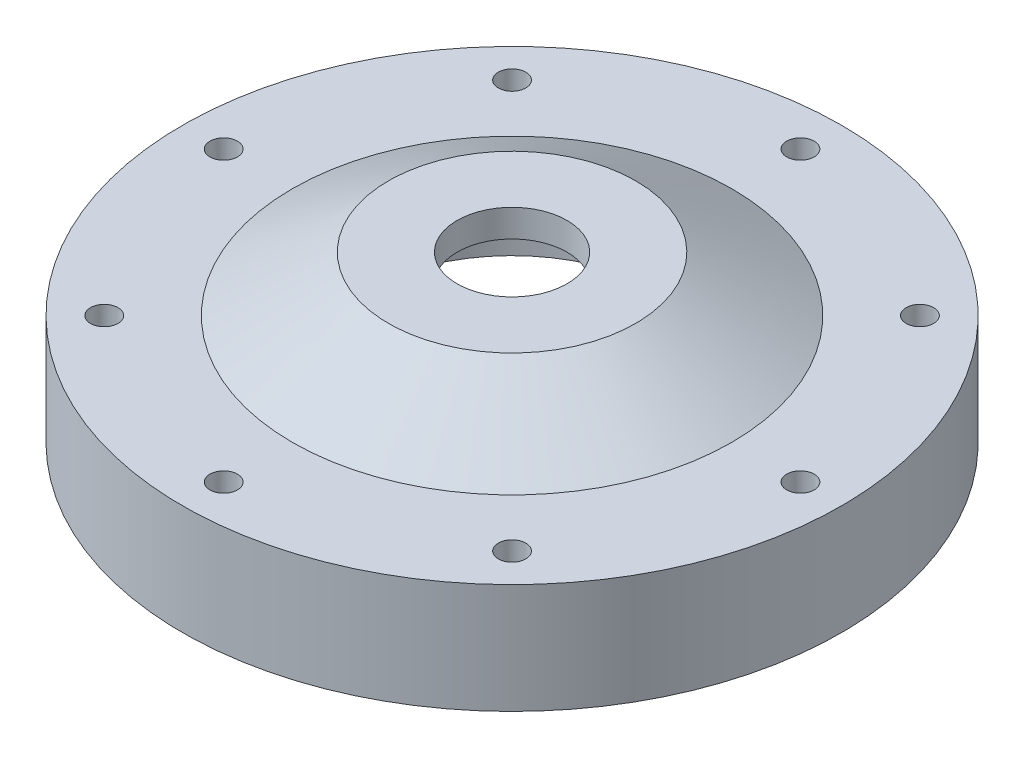
SolidWorks part; units mm, degrees
ref_plane "Front Plane" through (0, 0, 0) normal (0, 0, 1) x (1, 0, 0)
ref_plane "Top Plane" through (0, 0, 0) normal (0, 1, 0) x (1, 0, 0)
ref_plane "Right Plane" through (0, 0, 0) normal (1, 0, 0) x (0, 0, -1)
ref_axis "Axis1" through (0, 35.95, 0) along (0, -1, 0)
sketch "Sketch1" plane through (0, 0, 0) normal (0, 0, 1) x (1, 0, 0)
  line L0 (-12.7, 0) -> (-28.575, 0)
  line L1 (-76.2, -12.7) -> (-76.2, -38.1)
  line L4 (-76.2, -38.1) -> (-58.3057, -38.1)
  line L5 (-53.975, -38.1) -> (-53.975, -25.4)
  line L6 (-34.925, -19.05) -> (-12.7, -6.35)
  line L7 (-12.7, -6.35) -> (-12.7, 0)
  line L9 (0, 0) -> (0, 7.6805) construction
  line L10 (-36.5125, -25.4) -> (-34.925, -25.4)
  line L11 (-34.925, -25.4) -> (-34.925, -19.05)
  line L12 (-55.5625, -38.1) -> (-55.5625, -36.068)
  line L13 (-55.5625, -36.068) -> (-58.3057, -36.068)
  line L14 (-58.3057, -36.068) -> (-58.3057, -38.1)
  line L15 (-53.975, -38.1) -> (-55.5625, -38.1)
  line L16 (-36.5125, -25.4) -> (-36.5125, -23.368)
  line L17 (-36.5125, -23.368) -> (-39.2557, -23.368)
  line L18 (-39.2557, -23.368) -> (-39.2557, -25.4)
  line L19 (-39.2557, -25.4) -> (-53.975, -25.4)
  line L20 (-76.2, -12.7) -> (-50.8, -12.7)
  line L21 (-50.8, -12.7) -> (-28.575, 0)
  dimension "D1" = 34.925
  dimension "D2" = 22.225
  dimension "D3" = 76.2
  dimension "D4" = 2.7432
  dimension "D5" = 38.1
  dimension "D6" = 12.7
  dimension "D7" = 6.35
  dimension "D8" = 12.7
  dimension "D9" = 6.35
  dimension "D10" = 2.7432
  dimension "D11" = 2.032
  dimension "D12" = 1.5875
  dimension "D13" = 2.032
  dimension "D14" = 1.5875
  dimension "D15" = 12.7
  dimension "D16" = 25.4
  dimension "D17" = 15.875
revolve "Revolve1" add sketch "Sketch1" angle 360 about L9
sketch "Sketch2" plane through (0, 0, 0) normal (0, 1, 0) x (1, 0, 0)
  line L0 (0, 0) -> (-66.675, 0) construction
  point P4 (-66.675, 0)
  dimension "D1" = 66.675
hole_wizard "1/4 (0.25) Diameter Hole1" positions "3DSketch1" profile "Sketch3" hole size "1/4" standard "ANSI Inch" end condition through all
sketch3d "3DSketch1"
  point P0 (-66.675, 0, 0)
sketch "Sketch3" plane through (-66.675, 0, 0) normal (1, 0, 0) x (0, 0, 1)
  line L0 (0, 0) -> (0, 38.1)
  line L1 (0, 38.1) -> (3.175, 38.1)
  line L2 (3.175, 38.1) -> (3.175, 0)
  line L5 (3.175, 0) -> (0, 0)
  line L11 (0, -6.35) -> (0, 107.95) construction
  dimension "Thru Hole Dia." = 6.35
  dimension "Thru Hole Depth" = 38.1
pattern_circular "CirPattern1" count 8 over 360 about axis through (0, 35.95, 0) along (0, -1, 0) of "1/4 (0.25) Diameter Hole1"
